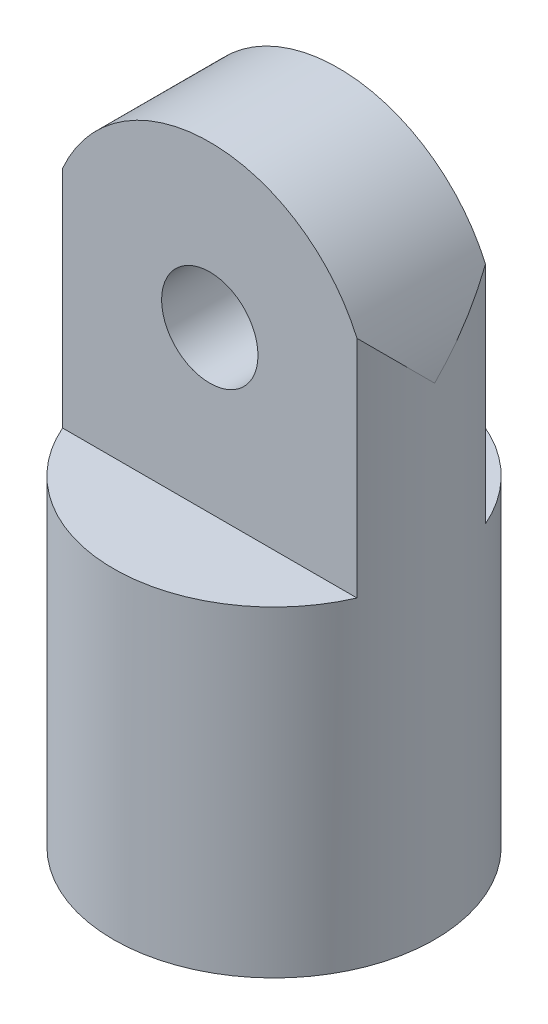
SolidWorks part; units mm, degrees
ref_plane "前视基准面" through (0, 0, 0) normal (0, 0, 1) x (1, 0, 0)
ref_plane "上视基准面" through (0, 0, 0) normal (0, 1, 0) x (1, 0, 0)
ref_plane "右视基准面" through (0, 0, 0) normal (1, 0, 0) x (0, 0, -1)
other "Configuration Table"
sketch "草图1" plane through (0, 0, 0) normal (0, 1, 0) x (1, 0, 0)
  circle A0 centre (0, 0) radius 50
  dimension "D1" = 100
extrude "凸台-拉伸1" add sketch "草图1" along normal blind 200
sketch "草图2" plane through (0, 0, 0) normal (1, 0, 0) x (0, 0, -1)
  line L0 (0, 55) -> (0, -55) construction
  line L1 (-70, 250) -> (70, 250)
  line L2 (-70, 250) -> (-70, 100)
  line L3 (-70, 100) -> (-20, 100)
  line L4 (70, 250) -> (70, 100)
  line L6 (-20, 100) -> (-20, 240)
  line L7 (-20, 240) -> (20, 240)
  line L8 (20, 100) -> (20, 240)
  line L9 (55, 0) -> (-55, 0) construction
  line L10 (20, 100) -> (70, 100)
  dimension "D1" = 20
  dimension "D2" = 50
  dimension "D3" = 20
  dimension "D4" = 50
  dimension "D5" = 100
  dimension "D6" = 150
  dimension "D7" = 10
extrude "切除-拉伸1" cut sketch "草图2" against normal blind 200 and the other way blind 200
sketch "草图3" plane through (0, 0, 20) normal (0, 0, 1) x (1, 0, 0)
  line L0 (0, -55) -> (0, 55) construction
  line L1 (45.8258, 100) -> (-45.8258, 100) construction
  line L2 (50, 150) -> (108.1804, 150)
  line L3 (-86.3288, 270) -> (108.1804, 270)
  line L4 (-86.3288, 270) -> (-86.3288, 150)
  line L5 (-86.3288, 150) -> (-50, 150)
  line L6 (108.1804, 270) -> (108.1804, 150)
  arc A0 (50, 150) -> (-50, 150) centre (0, 150) ccw
  dimension "D3" = 100
  dimension "D1" = 0
  dimension "D2" = 50
  dimension "D4" = 0
  dimension "D5" = 120
extrude "切除-拉伸4" cut sketch "草图3" against normal blind 200 and the other way blind 200
sketch "草图5" plane through (0, 0, 20) normal (0, 0, 1) x (1, 0, 0)
  line L0 (0, -55) -> (0, 55) construction
  line L1 (45.8258, 100) -> (-45.8258, 100) construction
  circle A0 centre (0, 150) radius 15
  dimension "D3" = 30
  dimension "D1" = 0
  dimension "D2" = 50
extrude "切除-拉伸5" cut sketch "草图5" against normal blind 200 and the other way blind 200
